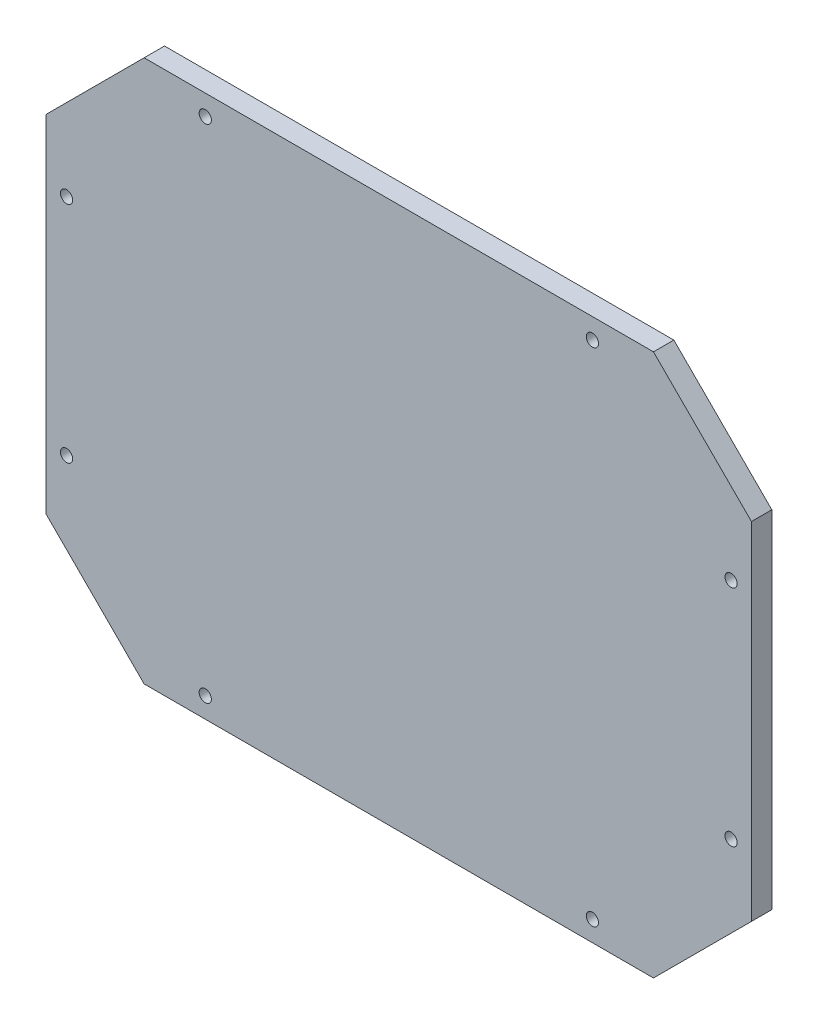
SolidWorks part; units mm, degrees
ref_plane "Front Plane" through (0, 0, 0) normal (0, 0, 1) x (1, 0, 0)
ref_plane "Top Plane" through (0, 0, 0) normal (0, 1, 0) x (1, 0, 0)
ref_plane "Right Plane" through (0, 0, 0) normal (1, 0, 0) x (0, 0, -1)
ref_plane "Plane1" through (0, 0, 5) normal (0, 0, 1) x (1, 0, 0)
sketch "Sketch1" plane through (0, 0, 5) normal (0, 0, 1) x (1, 0, 0)
  line L0 (4.8035, 37.5164) -> (41.5166, 61.7682)
  line L1 (41.5166, 61.7682) -> (54.7449, 41.7429)
  line L2 (54.7449, 41.7429) -> (18.0318, 17.4911)
  line L3 (18.0318, 17.4911) -> (4.8035, 37.5164)
  line L4 (18.0318, 115.5922) -> (54.7449, 91.3403)
  line L5 (54.7449, 91.3403) -> (41.5166, 71.315)
  line L6 (41.5166, 71.315) -> (4.8035, 95.5669)
  line L7 (4.8035, 95.5669) -> (18.0318, 115.5922)
  line L8 (70.2551, 41.7429) -> (83.4834, 61.7682)
  line L9 (83.4834, 61.7682) -> (120.1965, 37.5164)
  line L10 (120.1965, 37.5164) -> (106.9682, 17.4911)
  line L11 (106.9682, 17.4911) -> (70.2551, 41.7429)
  line L12 (83.4834, 71.315) -> (70.2551, 91.3403)
  line L13 (70.2551, 91.3403) -> (106.9682, 115.5922)
  line L14 (106.9682, 115.5922) -> (120.1965, 95.5669)
  line L15 (120.1965, 95.5669) -> (83.4834, 71.315)
  line L16 (-24.0416, 24.0416) -> (0, 0)
  line L17 (0, 0) -> (125, 0)
  line L18 (125, 0) -> (149.0416, 24.0416)
  line L19 (149.0416, 24.0416) -> (149.0416, 109.0416)
  line L20 (149.0416, 109.0416) -> (125, 133.0833)
  line L21 (125, 133.0833) -> (0, 133.0833)
  line L22 (0, 133.0833) -> (-24.0416, 109.0416)
  line L23 (-24.0416, 109.0416) -> (-24.0416, 24.0416)
  circle A0 centre (118.7314, 101.7761) radius 2.1
  circle A1 centre (78.347, 57.9841) radius 2.1
  circle A2 centre (53.2798, 85.1311) radius 2.1
  circle A3 centre (46.653, 57.9841) radius 2.1
  circle A4 centre (6.2686, 31.3071) radius 2.1
  circle A5 centre (6.2686, 101.7761) radius 2.1
  circle A6 centre (71.7202, 47.9522) radius 2.1
  circle A7 centre (78.347, 75.0991) radius 2.1
  circle A8 centre (112.1045, 111.8081) radius 2.1
  circle A9 centre (118.7314, 31.3071) radius 2.1
  circle A10 centre (46.653, 75.0991) radius 2.1
  circle A11 centre (53.2798, 47.9522) radius 2.1
  circle A12 centre (12.8955, 21.2752) radius 2.1
  circle A13 centre (12.8955, 111.8081) radius 2.1
  circle A14 centre (112.1045, 21.2752) radius 2.1
  circle A15 centre (71.7202, 85.1311) radius 2.1
  circle A16 centre (144.0416, 94.0416) radius 1.5
  circle A17 centre (-19.0416, 39.0416) radius 1.5
  circle A18 centre (144.0416, 39.0416) radius 1.5
  circle A19 centre (15, 5) radius 1.5
  circle A20 centre (110, 5) radius 1.5
  circle A21 centre (110, 128.0833) radius 1.5
  circle A22 centre (15, 128.0833) radius 1.5
  circle A23 centre (-19.0416, 94.0416) radius 1.5
extrude "Boss-Extrude1" add sketch "Sketch1" against normal blind 5
other "DeleteFace1" face at (69.6202, 47.9522, 0) face at (51.1798, 47.9522, 0) face at (44.553, 57.9841, 0) face at (4.1686, 31.3071, 0) face at (10.7955, 21.2752, 0) face at (76.247, 57.9841, 0) face at (76.247, 75.0991, 0) face at (69.6202, 85.1311, 0) face at (51.1798, 85.1311, 0) face at (44.553, 75.0991, 0) face at (116.6314, 31.3071, 0) face at (110.0045, 21.2752, 0) face at (116.6314, 101.7761, 0) face at (110.0045, 111.8081, 0) face at (10.7955, 111.8081, 0) face at (4.1686, 101.7761, 0) face at (36.3883, 103.4662, 2.5) face at (113.5823, 105.5795, 2.5) face at (101.8399, 49.6423, 2.5) face at (48.1307, 51.7556, 2.5) face at (23.1601, 49.6423, 2.5) face at (101.8399, 83.4409, 2.5) face at (113.5823, 27.5038, 2.5) face at (36.3883, 29.617, 2.5) face at (48.1307, 81.3277, 2.5) face at (11.4177, 105.5795, 2.5) face at (23.1601, 83.4409, 2.5) face at (88.6117, 103.4662, 2.5) face at (76.8693, 81.3277, 2.5) face at (76.8693, 51.7556, 2.5) face at (88.6117, 29.617, 2.5) face at (11.4177, 27.5038, 2.5) and patch yes
